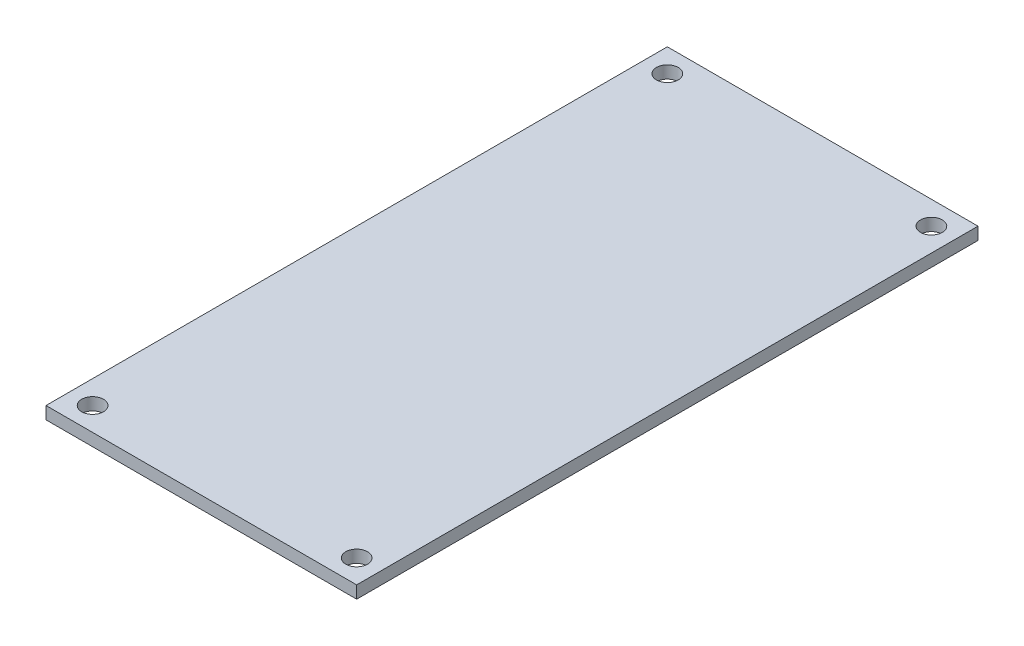
SolidWorks part; units mm, degrees
ref_plane "정면" through (0, 0, 0) normal (0, 0, 1) x (1, 0, 0)
ref_plane "윗면" through (0, 0, 0) normal (0, 1, 0) x (1, 0, 0)
ref_plane "우측면" through (0, 0, 0) normal (1, 0, 0) x (0, 0, -1)
sketch "스케치1" plane through (0, 0, 0) normal (0, 1, 0) x (1, 0, 0)
  line L0 (0, 50) -> (0, -50) construction
  line L5 (25, -50) -> (-25, -50)
  line L6 (25, -50) -> (25, 50)
  line L7 (25, 50) -> (-25, 50)
  line L8 (-25, -50) -> (-25, 50)
  line L9 (25, -50) -> (-25, 50) construction
  line L10 (25, 50) -> (-25, -50) construction
  line L11 (-25, 0) -> (25, 0) construction
  circle A0 centre (-21.25, 46.25) radius 1.75
  circle A1 centre (21.25, 46.25) radius 1.75
  circle A2 centre (21.25, -46.25) radius 1.75
  circle A3 centre (-21.25, -46.25) radius 1.75
  point P0 (0, 0)
  dimension "D3" = 3.5
  dimension "D1" = 50
  dimension "D2" = 100
  dimension "D4" = 3.75
  dimension "D5" = 3.75
extrude "보스-돌출1" add sketch "스케치1" along normal blind 2
ref_plane "평면1" through (-21.25, 0, 0) normal (1, 0, 0) x (0, 0, -1)
